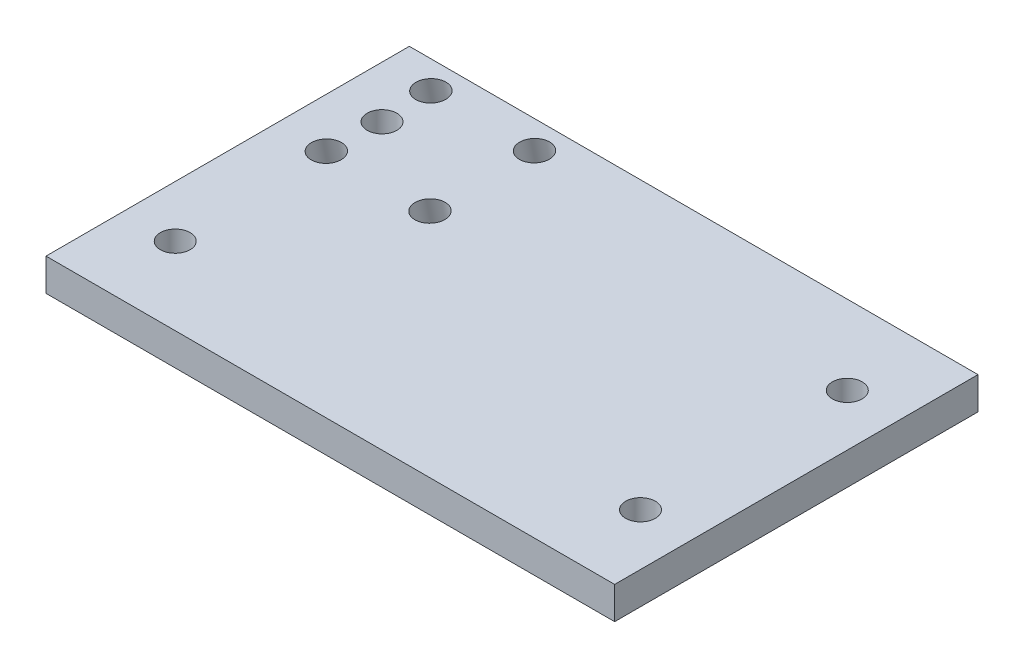
SolidWorks part; units mm, degrees
ref_plane "Front" through (0, 0, 0) normal (0, 0, 1) x (1, 0, 0)
ref_plane "Top" through (0, 0, 0) normal (0, 1, 0) x (1, 0, 0)
ref_plane "Right" through (0, 0, 0) normal (1, 0, 0) x (0, 0, -1)
sketch "Sketch1" plane through (0, 0, 0) normal (0, 1, 0) x (1, 0, 0)
  line L1 (0, 0) -> (90, 0)
  line L2 (0, 0) -> (0, 56.23)
  line L3 (0, 56.23) -> (90, 56.23)
  line L4 (90, 0) -> (90, 56.23)
  dimension "D1" = 90
  dimension "D2" = 56.23
extrude "Boss-Extrude1" add sketch "Sketch1" along normal blind 5
sketch "Sketch2" plane through (0, 5, 0) normal (0, 1, 0) x (1, 0, 0)
  circle A0 centre (82, 12) radius 2.3
  circle A1 centre (10, 12) radius 2.3
extrude "Cut-Extrude1" cut sketch "Sketch2" against normal blind 15
sketch "Sketch4" plane through (0, 5, 0) normal (0, 1, 0) x (1, 0, 0)
  circle A0 centre (39.2121, 27.5705) radius 2.2
  circle A1 centre (23.8176, 32.2728) radius 2.2
  circle A2 centre (43.572, 44.174) radius 2.2
  circle A3 centre (28.1775, 48.8763) radius 2.2
ref_plane "Plane1" through (0, 4.818, 0.9365) normal (0, 0.9816, 0.1908) x (1, 0, 0)
sketch "Sketch6" plane through (0, 4.818, 0.9365) normal (0, 0.9816, 0.1908) x (1, 0, 0)
  circle A0 centre (28.1775, 48.9324) radius 2.0398
  circle A1 centre (23.8176, 32.6339) radius 2.0398
  circle A2 centre (39.2121, 28.018) radius 2.0398
  circle A3 centre (43.572, 44.3165) radius 2.0398
sketch "Sketch7" plane through (0, 5, 0) normal (0, 1, 0) x (1, 0, 0)
  circle A0 centre (82, 44) radius 2.3
  circle A1 centre (10, 44) radius 2.3
extrude "Cut-Extrude3" cut sketch "Sketch7" against normal blind 45
sketch "Sketch8" plane through (0, 0, 0) normal (-1, 0, 0) x (0, 0, 1)
  circle A0 centre (-29.8532, 2.0033) radius 1.2661
sketch "Sketch9" plane through (0, 0, 0) normal (-1, 0, 0) x (0, 0, 1)
  line L1 (-56.23, 0) -> (4.9539, 0)
  line L2 (-56.23, 0) -> (-56.23, 5.0439)
  line L3 (-56.23, 5.0439) -> (4.9539, 5.0439)
  line L4 (4.9539, 0) -> (4.9539, 5.0439)
extrude "Cut-Extrude4" cut sketch "Sketch9" against normal blind 2
sketch "Sketch10" plane through (0, 0, 0) normal (0, -1, 0) x (-1, 0, 0)
  circle A0 centre (-9.6332, 36.7209) radius 2.3
  circle A1 centre (-25.671, 36.7209) radius 2.3
  circle A2 centre (-9.6332, 52.8988) radius 2.3
  circle A3 centre (-25.671, 52.8988) radius 2.3
sketch "Sketch11" plane through (0, 4.818, 0.9365) normal (0, 0.9816, 0.1908) x (1, 0, 0)
  circle A0 centre (9.6332, 51.9269) radius 2.3
  circle A1 centre (25.671, 51.9269) radius 2.3
  circle A2 centre (9.6332, 36.0462) radius 2.3
  circle A3 centre (25.671, 36.0462) radius 2.3
extrude "Cut-Extrude5" cut sketch "Sketch11" against normal blind 50
